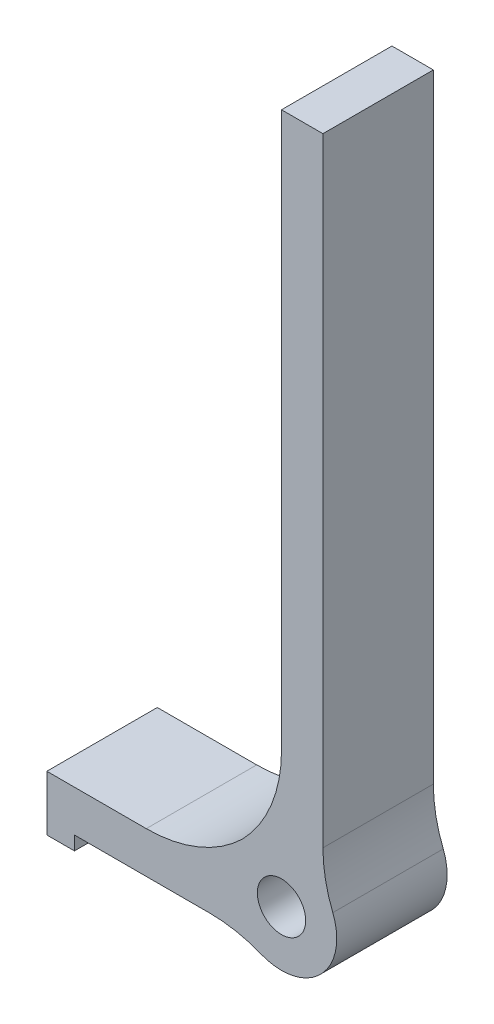
SolidWorks part; units mm, degrees
ref_plane "Front Plane" through (0, 0, 0) normal (0, 0, 1) x (1, 0, 0)
ref_plane "Top Plane" through (0, 0, 0) normal (0, 1, 0) x (1, 0, 0)
ref_plane "Right Plane" through (0, 0, 0) normal (1, 0, 0) x (0, 0, -1)
sketch "Sketch1" plane through (0, 0, 0) normal (0, 0, 1) x (1, 0, 0)
  line L0 (0, 0) -> (-2, 0)
  line L1 (-2, 0) -> (-2, 4)
  line L2 (-2, 4) -> (11, 4)
  line L3 (15, 8) -> (15, 54)
  line L4 (15, 54) -> (18, 54)
  line L5 (18, 54) -> (18, 6.6458)
  line L7 (0, 1) -> (0, 0)
  line L8 (12.3542, 1) -> (0, 1)
  line L9 (11, 4) -> (15, 4) construction
  line L10 (15, 4) -> (15, 8) construction
  arc A0 (15, 8) -> (11, 4) centre (15, 4) ccw
  circle A1 centre (15, 4) radius 1.75
  arc A2 (12.3542, 1) -> (18, 6.6458) centre (15, 4) ccw
  dimension "D6" = 3.5
  dimension "D7" = 8
  dimension "D1" = 1
  dimension "D2" = 2
  dimension "D3" = 15
  dimension "D4" = 50
  dimension "D5" = 3
  dimension "D8" = 3
extrude "Boss-Extrude1" add sketch "Sketch1" along normal blind 8
fillet "Fillet1" radius 10 4 edges at (12.3542, 1, 4) (18, 6.6458, 4) (15, 8, 4) (11, 4, 4)
